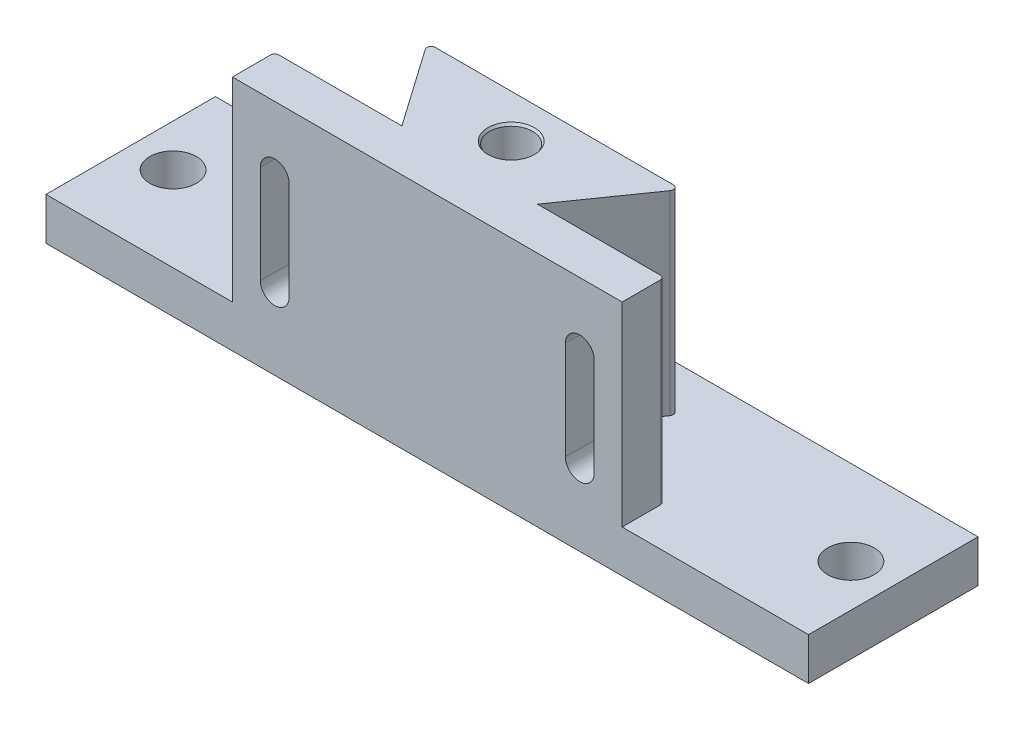
SolidWorks part; units mm, degrees
ref_plane "Front Plane" through (0, 0, 0) normal (0, 0, 1) x (1, 0, 0)
ref_plane "Top Plane" through (0, 0, 0) normal (0, 1, 0) x (1, 0, 0)
ref_plane "Right Plane" through (0, 0, 0) normal (1, 0, 0) x (0, 0, -1)
sketch "Sketch1" plane through (0, 0, 0) normal (0, 1, 0) x (1, 0, 0)
  line L0 (-1000, 10) -> (49000, 10) construction
  line L1 (0, 0) -> (70, 0)
  line L2 (0, 0) -> (0, 20)
  line L3 (0, 20) -> (70, 20)
  line L4 (70, 0) -> (70, 20)
  line L5 (35, -980) -> (35, 49020) construction
  line L6 (62.5, -20.8284) -> (62.5, 40.8284) construction
  line L7 (7.5, -20.1183) -> (7.5, 40.1183) construction
  line L8 (20, 15) -> (50, 15)
  line L9 (50, 15) -> (42.9979, 5)
  line L10 (42.9979, 5) -> (57.9979, 5)
  line L11 (27.0021, 5) -> (12.0021, 5)
  line L12 (20, 15) -> (27.0021, 5)
  line L13 (57.9979, 5) -> (57.9979, 0)
  line L14 (12.0021, 0) -> (12.0021, 5)
  line L16 (0, 20) -> (-10, 20)
  line L17 (0, 20) -> (0, 0)
  line L18 (0, 0) -> (-10, 0)
  line L19 (-10, 20) -> (-10, 0)
  line L20 (70, 0) -> (80, 0)
  line L21 (70, 0) -> (70, 20)
  line L22 (70, 20) -> (80, 20)
  line L23 (80, 0) -> (80, 20)
  point P8 (0, 10)
  point P11 (35, 20)
  point P14 (62.5, 10)
  point P17 (7.5, 10)
  point P24 (35, 15)
  dimension "D1" = 20
  dimension "D2" = 70
  dimension "D3" = 55
  dimension "D4" = 27.5
  dimension "D5" = 55
  dimension "D6" = 5
  dimension "D7" = 5
  dimension "D8" = 15
  dimension "D9" = 15
  dimension "D10" = 15
  dimension "D11" = 10
  dimension "D12" = 10
  dimension "D13" = 20
extrude "Boss-Extrude1" add sketch "Sketch1" along normal blind 5 contours L8 L12 L11 L2 L1 L4 L10 L9 | L12 L8 L9 L10 L4 L3 L2 L11 | L16 L19 L18 L2 | L20 L23 L22 L4 region at (0.728, 0, -10) region at (-5, 0, -10) region at (35, 0, -6.5037) region at (75, 0, -10)
extrude "Boss-Extrude2" add sketch "Sketch1<3>" along normal blind 28 contours L8 L12 L11 L2 L1 L4 L10 L9 region at (35, 0, -6.5037)
sketch "Sketch1<3>" plane through (0, 0, 0) normal (0, 1, 0) x (1, 0, 0) same geometry as "Sketch1"
hole_wizard "M5 Clearance Hole1" positions "Sketch2" profile "Sketch3" hole size "M5" standard "ANSI Metric"
sketch "Sketch2" plane through (0, 5, 0) normal (0, 1, 0) x (1, 0, 0)
  line L0 (-10, 20) -> (80, 20) construction
  line L1 (80, 0) -> (80, 20) construction
  line L2 (-10, 20) -> (-10, 0) construction
  point P0 (75, 10)
  point P2 (-5, 10)
  dimension "D1" = 10
  dimension "D2" = 10
  dimension "D3" = 5
  dimension "D4" = 5
sketch "Sketch3" plane through (75, 5, -10) normal (1, 0, 0) x (0, 0, 1)
  line L0 (0, 0) -> (0, 11.6524)
  line L1 (0, 11.6524) -> (2.75, 10)
  line L2 (2.75, 10) -> (2.75, 0)
  line L5 (2.75, 0) -> (0, 0)
  line L10 (0, 11.6524) -> (-2.75, 10) construction
  line L11 (0, -6.35) -> (0, 107.95) construction
  dimension "Hole Dia." = 5.5
  dimension "Hole Depth" = 10
  dimension "Drill Angle" = 118
hole_wizard "CSK for M4 Flat Head Machine Screw1" positions "Sketch4" profile "Sketch6" countersink size "M4" standard "ANSI Metric"
sketch "Sketch4" plane through (0, 28, 0) normal (0, 1, 0) x (1, 0, 0)
  line L0 (12.0021, 0) -> (57.9979, 0) construction
  line L1 (80, 0) -> (80, 20) construction
  point P0 (35, 9.9)
  dimension "D1" = 9.9
  dimension "D2" = 45
sketch "Sketch6" plane through (35, 28, -9.9) normal (1, 0, 0) x (0, 0, 1)
  line L0 (0, 0) -> (0, 16.5322)
  line L1 (0, 16.5322) -> (2.55, 15)
  line L2 (2.55, 15) -> (2.55, 0.2856)
  line L3 (2.55, 0.2856) -> (2.75, 0)
  line L5 (2.75, 0) -> (0, 0)
  line L6 (-2.55, 0.2856) -> (-2.75, 0) construction
  line L10 (0, 16.5322) -> (-2.55, 15) construction
  line L11 (0, -6.35) -> (0, 107.95) construction
  dimension "Hole Dia." = 5.1
  dimension "Hole Depth" = 15
  dimension "Near C'Sink Dia." = 5.5
  dimension "Near C'Sink Angle" = 70
  dimension "Drill Angle" = 118
fillet "Fillet1" radius 0.5 4 edges at (20, 16.5, -15) (50, 16.5, -15) (57.9979, 16.5, -5) (12.0021, 16.5, -5)
hole_wizard "M3 Clearance Slot1" positions "Sketch9" profile "Sketch10" size "M3" standard "ANSI Metric" slot yes
sketch "Sketch9" plane through (0, 0, 0) normal (0, 0, 1) x (1, 0, 0)
  line L0 (17.0021, 7.1357) -> (17.0021, 22.1357) construction
  line L2 (12.0021, 28) -> (12.0021, 5) construction
  line L3 (57.9979, 28) -> (57.9979, 5) construction
  point P0 (17.0021, 14.6357)
  point P4 (52.9979, 14.6357)
  dimension "D1" = 15
  dimension "D2" = 5
  dimension "D3" = 5
sketch "Sketch10" plane through (17.0021, 14.6357, 0) normal (1, 0, 0) x (0, -1, 0)
  line L0 (0, 0) -> (0, 7.0215)
  line L1 (0, 7.0215) -> (1.7, 6)
  line L2 (1.7, 6) -> (1.7, 0)
  line L5 (1.7, 0) -> (0, 0)
  line L10 (0, 7.0215) -> (-1.7, 6) construction
  line L11 (0, -6.35) -> (0, 107.95) construction
  dimension "Hole Dia." = 3.4
  dimension "Hole Depth" = 6
  dimension "Drill Angle" = 118
